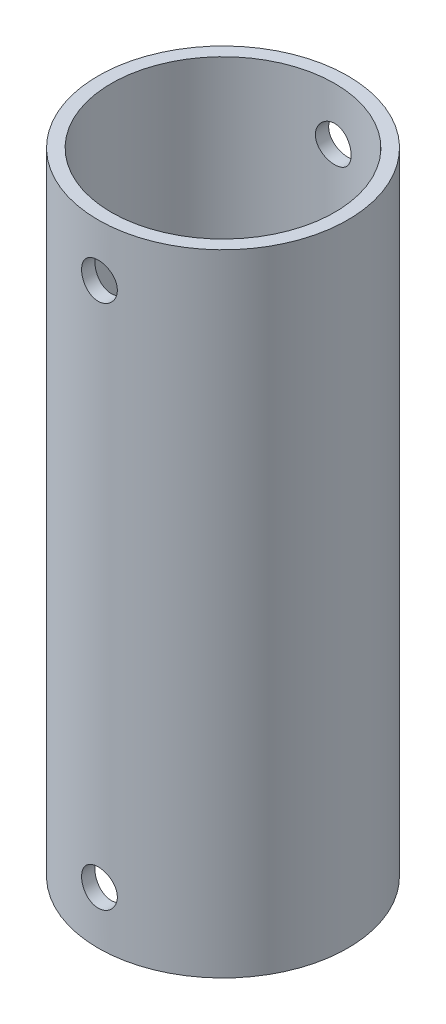
SolidWorks part; units mm, degrees
ref_plane "Front Plane" through (0, 0, 0) normal (0, 0, 1) x (1, 0, 0)
ref_plane "Top Plane" through (0, 0, 0) normal (0, 1, 0) x (1, 0, 0)
ref_plane "Right Plane" through (0, 0, 0) normal (1, 0, 0) x (0, 0, -1)
sketch "Sketch1" plane through (0, 0, 0) normal (0, 1, 0) x (1, 0, 0)
  circle A0 centre (0, 0) radius 30.1625
  circle A1 centre (0, 0) radius 26.9875
extrude "Boss-Extrude1" add sketch "Sketch1" along normal blind 76.2 and the other way blind 76.2
sketch "Sketch2" plane through (0, 0, 0) normal (0, 0, 1) x (1, 0, 0)
  line L0 (0, 63.5) -> (0, 76.2) construction
  line L1 (26.9875, 76.2) -> (-26.9875, 76.2) construction
  line L2 (0, -76.2) -> (0, -63.5) construction
  line L3 (-30.1625, -76.2) -> (30.1625, -76.2) construction
  circle A0 centre (0, 63.5) radius 4.318
  circle A1 centre (0, -63.5) radius 4.318
  dimension "D1" = 8.636
  dimension "D4" = 8.636
  dimension "D2" = 12.7
  dimension "D3" = 12.7
extrude "Cut-Extrude1" cut sketch "Sketch2" against normal up to next and the other way up to next
